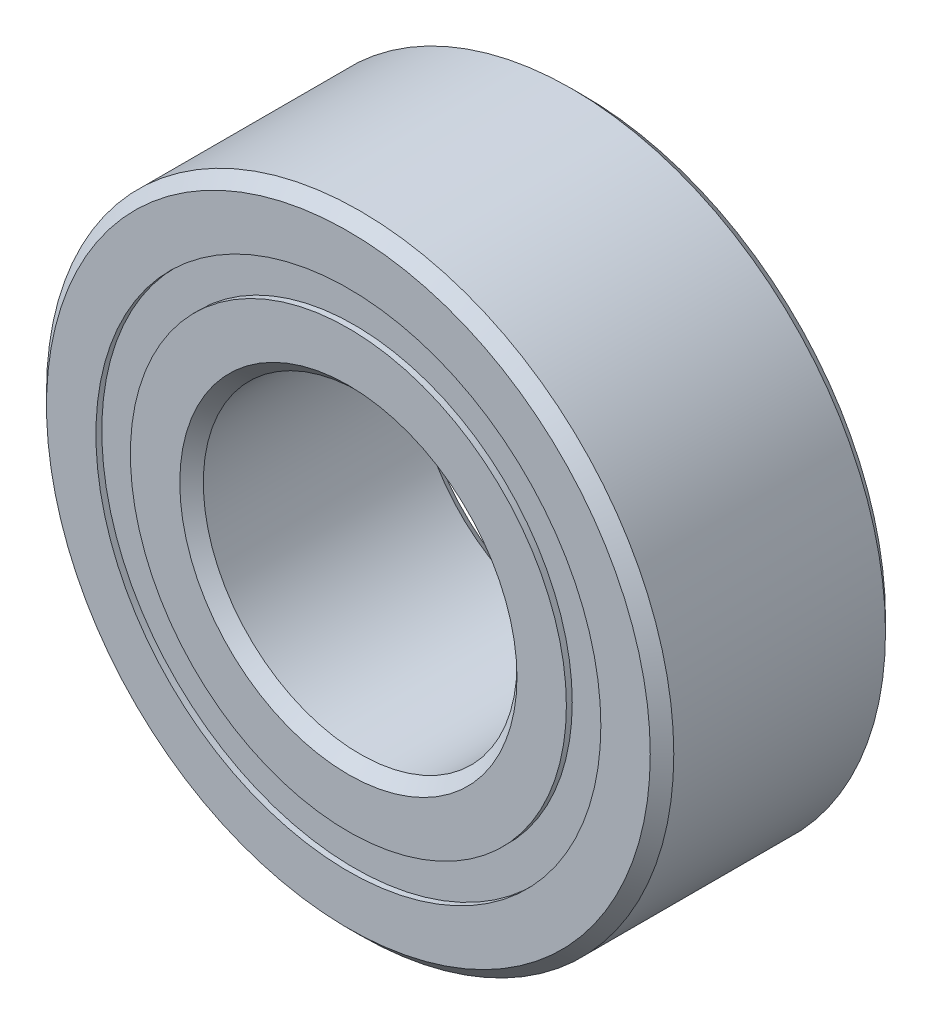
SolidWorks part; units mm, degrees
ref_plane "Front Plane" through (0, 0, 0) normal (0, 0, 1) x (1, 0, 0)
ref_plane "Top Plane" through (0, 0, 0) normal (0, 1, 0) x (1, 0, 0)
ref_plane "Right Plane" through (0, 0, 0) normal (1, 0, 0) x (0, 0, -1)
sketch "Sketch1" plane through (0, 0, 0) normal (1, 0, 0) x (0, 0, -1)
  line L0 (-2.3813, 0) -> (2.3813, 0) construction
  line L1 (0, 6.35) -> (0, -6.35) construction
  line L2 (2.1431, 6.35) -> (-2.1431, 6.35)
  line L3 (-2.1431, 6.35) -> (-2.3813, 6.1119)
  line L4 (-2.3813, 6.1119) -> (-2.3813, 5.1114)
  line L5 (-2.3813, 5.1114) -> (-1.0583, 5.1114)
  line L6 (2.3813, 5.1114) -> (1.0583, 5.1114)
  line L7 (2.3813, 6.1119) -> (2.3813, 5.1114)
  line L8 (2.1431, 6.35) -> (2.3813, 6.1119)
  line L9 (0, 6.35) -> (0, 4.7625) construction
  line L10 (0, 4.7625) -> (0, 3.175) construction
  arc A0 (-1.0583, 5.1114) -> (1.0583, 5.1114) centre (0, 4.7625) cw
  point P14 (0, 3.175)
  dimension "Width" = 4.7625
  dimension "OD" = 12.7
  dimension "D1" = 45
  dimension "D2" = 0.2381
  dimension "D3" = 2.1167
  dimension "D4" = 0.3489
revolve "Revolve1" add sketch "Sketch1" angle 360 about L0
sketch "Sketch3" plane through (0, 0, 0) normal (1, 0, 0) x (0, 0, -1)
  line L0 (-1.0583, 4.4136) -> (-2.3813, 4.4136)
  line L1 (-2.3813, 6.1119) -> (-2.3813, 5.1114) construction
  line L2 (-2.1431, 6.35) -> (-2.3813, 6.1119) construction
  line L3 (-2.3813, 4.4136) -> (-2.3813, 3.4131)
  line L5 (-2.3813, 3.4131) -> (-2.1431, 3.175)
  line L6 (-2.1431, 3.175) -> (2.1431, 3.175)
  line L7 (2.1431, 6.35) -> (2.1431, -6.35) construction
  line L8 (2.1431, 3.175) -> (2.3812, 3.4131)
  line L9 (2.3813, -6.1119) -> (2.3813, 6.1119) construction
  line L10 (2.3812, 3.4131) -> (2.3813, 4.4136)
  line L11 (2.3813, 4.4136) -> (1.0583, 4.4136)
  line L12 (0, 6.35) -> (0, -6.35) construction
  line L13 (2.1431, 6.35) -> (2.3813, 6.1119) construction
  arc A1 (1.0583, 4.4136) -> (-1.0583, 4.4136) centre (0, 4.7625) cw
  arc A2 (1.0583, 5.1114) -> (-1.0583, 5.1114) centre (0, 4.7625) ccw construction
revolve "Revolve3" add sketch "Sketch3" angle 360 about L0
sketch "Sketch4" plane through (0, 0, 0) normal (1, 0, 0) x (0, 0, -1)
  line L0 (-1.1144, 4.7625) -> (1.1144, 4.7625)
  arc A2 (-1.1144, 4.7625) -> (1.1144, 4.7625) centre (0, 4.7625) cw
  arc A3 (1.0583, 5.1114) -> (-1.0583, 5.1114) centre (0, 4.7625) ccw construction
revolve "Revolve4" add sketch "Sketch4" angle 360 about L0
ref_axis "Axis1" through (0, 0, -2.3813) along (0, 0, 1)
pattern_circular "CirPattern1" count 12 every 30 about axis through (0, 0, -2.3813) along (0, 0, 1) of bodies 104
sketch "Sketch5" plane through (0, 0, 0) normal (1, 0, 0) x (0, 0, -1)
  line L0 (-2.3813, 5.1114) -> (-1.0583, 5.1114) construction
  line L1 (-2.2622, 5.1114) -> (-1.1144, 5.1114)
  line L2 (-2.2622, 5.1114) -> (-2.2622, 4.4136)
  line L3 (-2.2622, 4.4136) -> (-1.1144, 4.4136)
  line L4 (-1.1144, 5.1114) -> (-1.1144, 4.4136)
  line L5 (-1.0583, 4.4136) -> (-2.3813, 4.4136) construction
  line L6 (2.3813, 5.1114) -> (1.0583, 5.1114) construction
  line L7 (2.2622, 5.1114) -> (1.1144, 5.1114)
  line L8 (2.2622, 5.1114) -> (2.2622, 4.4136)
  line L9 (2.2622, 4.4136) -> (1.1144, 4.4136)
  line L10 (1.1144, 5.1114) -> (1.1144, 4.4136)
  line L11 (2.3813, 4.4136) -> (1.0583, 4.4136) construction
  line L12 (-2.1431, 6.35) -> (-2.3813, 6.1119) construction
  point P18 (-2.2622, 6.2309)
revolve "Revolve5" add sketch "Sketch5" angle 360 about L0
equation "\"D2@Sketch1\" = \"Width@Sketch1\"*.05"
equation "\"D3@Sketch1\" = \"Width@Sketch1\"/2.25"
equation "\"D4@Sketch1\" = (((\"OD@Sketch1\"-\"Width@Sketch1\")/2)/3.25)/3.5"
equation "\"D2@CirPattern1\" = 360/\"Balls@CirPattern1\""
